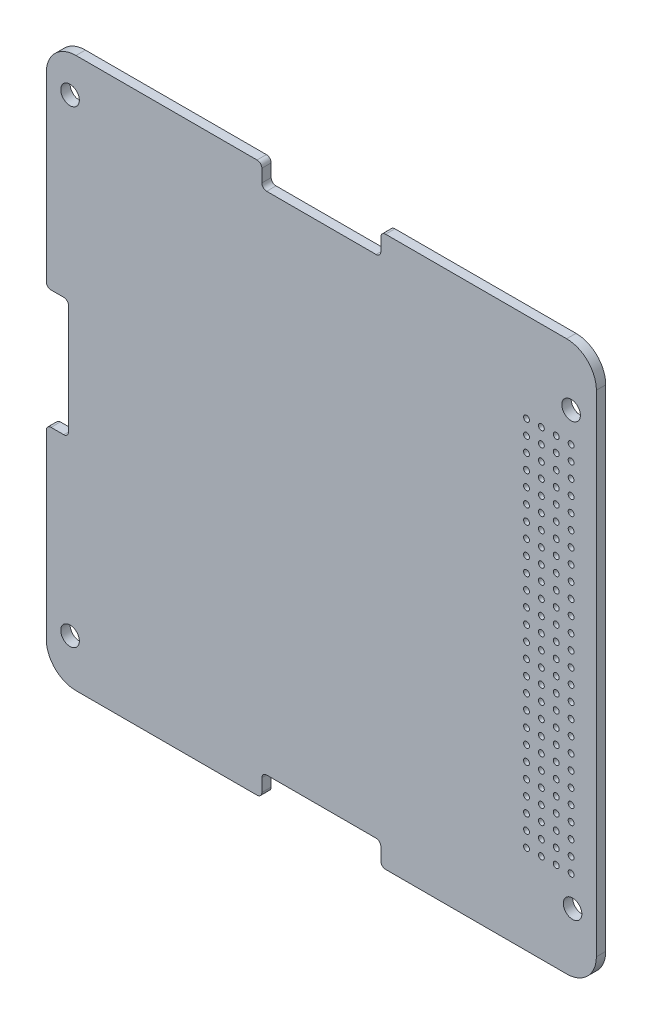
SolidWorks part; units mm, degrees
ref_plane "Front Plane" through (0, 0, 0) normal (0, 0, 1) x (1, 0, 0)
ref_plane "Top Plane" through (0, 0, 0) normal (0, 1, 0) x (1, 0, 0)
ref_plane "Right Plane" through (0, 0, 0) normal (1, 0, 0) x (0, 0, -1)
sketch "Sketch1" plane through (0, 0, 0) normal (0, 0, 1) x (1, 0, 0)
  line L0 (5.08, 0) -> (36.0124, 0)
  line L1 (36.83, 0.8176) -> (36.83, 2.9924)
  line L2 (37.6476, 3.81) -> (56.3324, 3.81)
  line L3 (57.15, 2.9924) -> (57.15, 0.8176)
  line L4 (57.9676, 0) -> (88.9, 0)
  line L5 (93.98, 5.08) -> (93.98, 88.9)
  line L6 (88.9, 93.98) -> (57.9676, 93.98)
  line L7 (57.15, 93.1624) -> (57.15, 90.9876)
  line L8 (56.3324, 90.17) -> (37.6476, 90.17)
  line L9 (36.83, 90.9876) -> (36.83, 93.1624)
  line L10 (36.0124, 93.98) -> (5.08, 93.98)
  line L11 (0, 88.9) -> (0, 57.9676)
  line L12 (0.8176, 57.15) -> (2.9924, 57.15)
  line L13 (3.81, 56.3324) -> (3.81, 37.6476)
  line L14 (2.9924, 36.83) -> (0.8176, 36.83)
  line L15 (0, 36.0124) -> (0, 5.08)
  arc A0 (5.08, 0) -> (0, 5.08) centre (5.08, 5.08) cw
  arc A1 (88.9, 0) -> (93.98, 5.08) centre (88.9, 5.08) ccw
  arc A2 (93.98, 88.9) -> (88.9, 93.98) centre (88.9, 88.9) ccw
  arc A3 (5.08, 93.98) -> (0, 88.9) centre (5.08, 88.9) ccw
  arc A4 (57.15, 0.8176) -> (57.9676, 0) centre (57.9676, 0.8176) ccw
  arc A5 (56.3324, 3.81) -> (57.15, 2.9924) centre (56.3324, 2.9924) cw
  arc A6 (36.83, 2.9924) -> (37.6476, 3.81) centre (37.6476, 2.9924) cw
  arc A7 (36.0124, 0) -> (36.83, 0.8176) centre (36.0124, 0.8176) ccw
  arc A8 (0.8176, 36.83) -> (0, 36.0124) centre (0.8176, 36.0124) ccw
  arc A9 (3.81, 37.6476) -> (2.9924, 36.83) centre (2.9924, 37.6476) cw
  arc A10 (2.9924, 57.15) -> (3.81, 56.3324) centre (2.9924, 56.3324) cw
  arc A11 (0, 57.9676) -> (0.8176, 57.15) centre (0.8176, 57.9676) ccw
  arc A12 (36.83, 93.1624) -> (36.0124, 93.98) centre (36.0124, 93.1624) ccw
  arc A13 (37.6476, 90.17) -> (36.83, 90.9876) centre (37.6476, 90.9876) cw
  arc A14 (57.15, 90.9876) -> (56.3324, 90.17) centre (56.3324, 90.9876) cw
  arc A15 (57.9676, 93.98) -> (57.15, 93.1624) centre (57.9676, 93.1624) ccw
  circle A16 centre (82.042, 78.74) radius 0.5
  circle A17 centre (84.582, 78.74) radius 0.5
  circle A18 centre (87.122, 78.74) radius 0.5
  circle A19 centre (89.662, 78.74) radius 0.5
  circle A20 centre (84.582, 76.2) radius 0.5
  circle A21 centre (87.122, 76.2) radius 0.5
  circle A22 centre (89.662, 76.2) radius 0.5
  circle A23 centre (84.582, 73.66) radius 0.5
  circle A24 centre (87.122, 73.66) radius 0.5
  circle A25 centre (89.662, 73.66) radius 0.5
  circle A26 centre (84.582, 71.12) radius 0.5
  circle A27 centre (87.122, 71.12) radius 0.5
  circle A28 centre (89.662, 71.12) radius 0.5
  circle A29 centre (84.582, 68.58) radius 0.5
  circle A30 centre (87.122, 68.58) radius 0.5
  circle A31 centre (89.662, 68.58) radius 0.5
  circle A32 centre (84.582, 66.04) radius 0.5
  circle A33 centre (87.122, 66.04) radius 0.5
  circle A34 centre (89.662, 66.04) radius 0.5
  circle A35 centre (84.582, 63.5) radius 0.5
  circle A36 centre (87.122, 63.5) radius 0.5
  circle A37 centre (89.662, 63.5) radius 0.5
  circle A38 centre (84.582, 60.96) radius 0.5
  circle A39 centre (87.122, 60.96) radius 0.5
  circle A40 centre (89.662, 60.96) radius 0.5
  circle A41 centre (84.582, 58.42) radius 0.5
  circle A42 centre (87.122, 58.42) radius 0.5
  circle A43 centre (89.662, 58.42) radius 0.5
  circle A44 centre (84.582, 55.88) radius 0.5
  circle A45 centre (87.122, 55.88) radius 0.5
  circle A46 centre (89.662, 55.88) radius 0.5
  circle A47 centre (84.582, 53.34) radius 0.5
  circle A48 centre (87.122, 53.34) radius 0.5
  circle A49 centre (89.662, 53.34) radius 0.5
  circle A50 centre (84.582, 50.8) radius 0.5
  circle A51 centre (87.122, 50.8) radius 0.5
  circle A52 centre (89.662, 50.8) radius 0.5
  circle A53 centre (84.582, 48.26) radius 0.5
  circle A54 centre (87.122, 48.26) radius 0.5
  circle A55 centre (89.662, 48.26) radius 0.5
  circle A56 centre (84.582, 45.72) radius 0.5
  circle A57 centre (87.122, 45.72) radius 0.5
  circle A58 centre (89.662, 45.72) radius 0.5
  circle A59 centre (84.582, 43.18) radius 0.5
  circle A60 centre (87.122, 43.18) radius 0.5
  circle A61 centre (89.662, 43.18) radius 0.5
  circle A62 centre (84.582, 40.64) radius 0.5
  circle A63 centre (87.122, 40.64) radius 0.5
  circle A64 centre (89.662, 40.64) radius 0.5
  circle A65 centre (84.582, 38.1) radius 0.5
  circle A66 centre (87.122, 38.1) radius 0.5
  circle A67 centre (89.662, 38.1) radius 0.5
  circle A68 centre (84.582, 35.56) radius 0.5
  circle A69 centre (87.122, 35.56) radius 0.5
  circle A70 centre (89.662, 35.56) radius 0.5
  circle A71 centre (84.582, 33.02) radius 0.5
  circle A72 centre (87.122, 33.02) radius 0.5
  circle A73 centre (89.662, 33.02) radius 0.5
  circle A74 centre (84.582, 30.48) radius 0.5
  circle A75 centre (87.122, 30.48) radius 0.5
  circle A76 centre (89.662, 30.48) radius 0.5
  circle A77 centre (84.582, 27.94) radius 0.5
  circle A78 centre (87.122, 27.94) radius 0.5
  circle A79 centre (89.662, 27.94) radius 0.5
  circle A80 centre (84.582, 25.4) radius 0.5
  circle A81 centre (87.122, 25.4) radius 0.5
  circle A82 centre (89.662, 25.4) radius 0.5
  circle A83 centre (84.582, 22.86) radius 0.5
  circle A84 centre (87.122, 22.86) radius 0.5
  circle A85 centre (89.662, 22.86) radius 0.5
  circle A86 centre (84.582, 20.32) radius 0.5
  circle A87 centre (87.122, 20.32) radius 0.5
  circle A88 centre (89.662, 20.32) radius 0.5
  circle A89 centre (84.582, 17.78) radius 0.5
  circle A90 centre (87.122, 17.78) radius 0.5
  circle A91 centre (89.662, 17.78) radius 0.5
  circle A92 centre (84.582, 15.24) radius 0.5
  circle A93 centre (87.122, 15.24) radius 0.5
  circle A94 centre (89.662, 15.24) radius 0.5
  circle A95 centre (82.042, 76.2) radius 0.5
  circle A96 centre (82.042, 73.66) radius 0.5
  circle A97 centre (82.042, 71.12) radius 0.5
  circle A98 centre (82.042, 68.58) radius 0.5
  circle A99 centre (82.042, 66.04) radius 0.5
  circle A100 centre (82.042, 63.5) radius 0.5
  circle A101 centre (82.042, 60.96) radius 0.5
  circle A102 centre (82.042, 58.42) radius 0.5
  circle A103 centre (82.042, 55.88) radius 0.5
  circle A104 centre (82.042, 53.34) radius 0.5
  circle A105 centre (82.042, 50.8) radius 0.5
  circle A106 centre (82.042, 48.26) radius 0.5
  circle A107 centre (82.042, 45.72) radius 0.5
  circle A108 centre (82.042, 43.18) radius 0.5
  circle A109 centre (82.042, 40.64) radius 0.5
  circle A110 centre (82.042, 38.1) radius 0.5
  circle A111 centre (82.042, 35.56) radius 0.5
  circle A112 centre (82.042, 33.02) radius 0.5
  circle A113 centre (82.042, 30.48) radius 0.5
  circle A114 centre (82.042, 27.94) radius 0.5
  circle A115 centre (82.042, 25.4) radius 0.5
  circle A116 centre (82.042, 22.86) radius 0.5
  circle A117 centre (82.042, 20.32) radius 0.5
  circle A118 centre (82.042, 17.78) radius 0.5
  circle A119 centre (82.042, 15.24) radius 0.5
  circle A120 centre (89.916, 10.16) radius 1.5875
  circle A121 centre (89.662, 83.82) radius 1.5875
  circle A123 centre (4.064, 7.62) radius 1.5875
  circle A124 centre (4.064, 87.63) radius 1.5875
  point P20 (0, 0)
  point P268 (0, 0)
  point P272 (0, 0)
  dimension "D7" = 5.08
  dimension "D8" = 0.8176
  dimension "D9" = 1
  dimension "D12" = 80.01
  dimension "D18" = 3.175
  dimension "D19" = 3.81
  dimension "D1" = 93.98
  dimension "D2" = 93.98
  dimension "D3" = 36.83
  dimension "D4" = 3.81
  dimension "D5" = 3.81
  dimension "D6" = 3.81
  dimension "D13" = 73.66
  dimension "D14" = 5.08
  dimension "D15" = 15.24
  dimension "D16" = 85.598
  dimension "D17" = 85.852
  dimension "D20" = 4.064
  dimension "D10" = 4
  dimension "D11" = 26
extrude "Boss-Extrude2" add sketch "Sketch1" along normal blind 1.6
